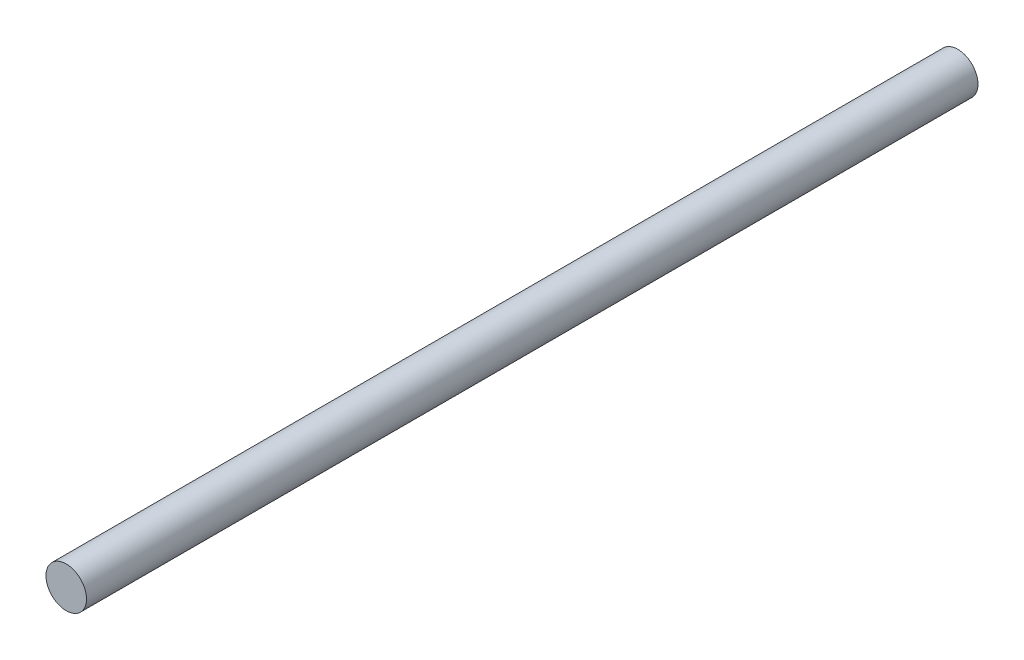
SolidWorks part; units mm, degrees
ref_plane "Front Plane" through (0, 0, 0) normal (0, 0, 1) x (1, 0, 0)
ref_plane "Top Plane" through (0, 0, 0) normal (0, 1, 0) x (1, 0, 0)
ref_plane "Right Plane" through (0, 0, 0) normal (1, 0, 0) x (0, 0, -1)
sketch "Sketch2" plane through (0, 0, 0) normal (0, 0, 1) x (1, 0, 0)
  circle A0 centre (0, 0) radius 3.175
  dimension "D1" = 6.35
extrude "Boss-Extrude1" add sketch "Sketch2" along normal blind 139.7
